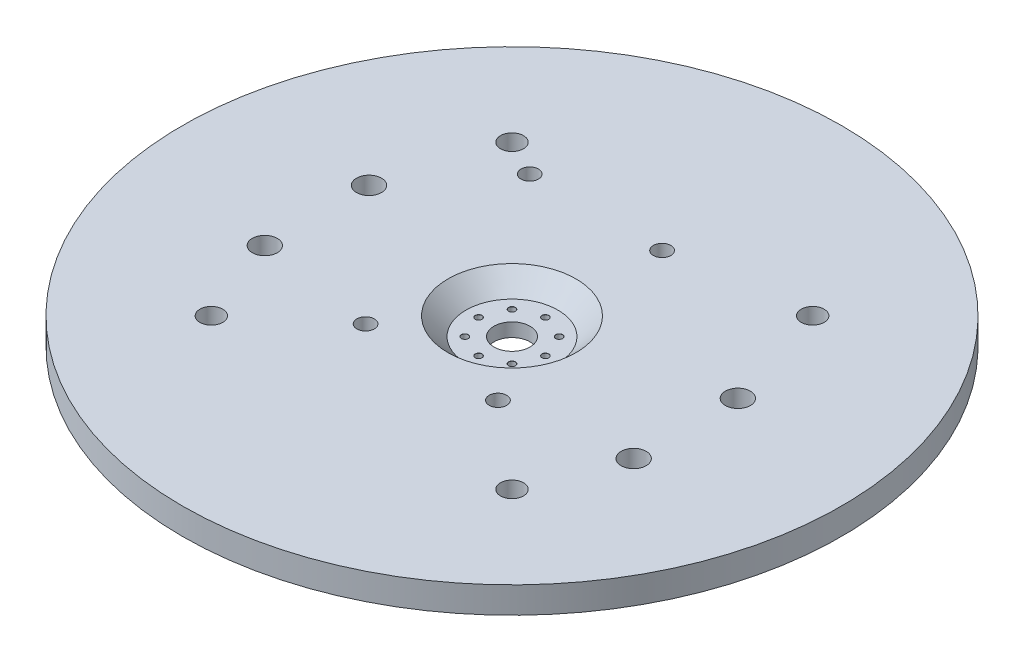
SolidWorks part; units mm, degrees
other "Markup1"
sketch "Sketch21" plane through (-65.5, -15.05, -60) normal (-0.0927, -0.2854, -0.9539) x (0.9951, -0.0609, -0.0785)
material "6061 Alloy"
ref_plane "Front Plane" through (0, 0, 0) normal (0, 0, 1) x (1, 0, 0)
ref_plane "Top Plane" through (0, 0, 0) normal (0, 1, 0) x (1, 0, 0)
ref_plane "Right Plane" through (0, 0, 0) normal (1, 0, 0) x (0, 0, -1)
sketch "Sketch1" plane through (0, 0, 0) normal (0, 1, 0) x (1, 0, 0)
  circle A0 centre (0, 0) radius 79.0575
  dimension "D1" = 158.115
extrude "Boss-Extrude1" add sketch "Sketch1" along normal mid plane 6.3246
sketch "Sketch2" plane through (0, -3.1623, 0) normal (0, -1, 0) x (1, 0, 0)
  circle A0 centre (0, 0) radius 12.065
  circle A1 centre (0, 0) radius 79.0575 construction
  dimension "D1" = 24.13
sketch "Sketch5" plane through (0, 3.1623, 0) normal (0, 1, 0) x (1, 0, 0)
  circle A0 centre (0, 0) radius 10.4
  circle A1 centre (0, 0) radius 79.0575 construction
  dimension "D1" = 20.8
hole_wizard "Tap Drill for M5x0.8 Tap1" positions "Sketch22" profile "Sketch23" hole size "M5x0.8" standard "ANSI Metric" end condition through all
sketch "Sketch22" plane through (0, 3.1623, 0) normal (0, 1, 0) x (1, 0, 0)
  point P0 (-27.3188, 31.5712)
  point P3 (4.4312, 31.5712)
  point P6 (-15.875, -19.2459)
  point P9 (15.875, -19.2459)
  dimension "D1" = 31.75
  dimension "D2" = 31.5712
  dimension "D3" = 4.4312
  dimension "D4" = 31.75
  dimension "D5" = 19.2459
  dimension "D6" = 15.875
sketch "Sketch23" plane through (-27.3188, 3.1623, -31.5712) normal (1, 0, 0) x (0, 0, 1)
  line L0 (0, 0) -> (0, 6.3246)
  line L1 (0, 6.3246) -> (2.1, 6.3246)
  line L2 (2.1, 6.3246) -> (2.1, 0)
  line L5 (2.1, 0) -> (0, 0)
  line L11 (0, -6.35) -> (0, 107.95) construction
  dimension "Thru Hole Dia." = 4.2
  dimension "Thru Hole Depth" = 6.3246
hole_wizard "Tap Drill for M7x1.0 Tap1" positions "Sketch24" profile "Sketch25" hole size "M7x1.0" standard "ANSI Metric" end condition through all
sketch "Sketch24" plane through (0, 3.1623, 0) normal (0, 1, 0) x (1, 0, 0)
  point P0 (-44.245, 9.9416)
  point P3 (-44.245, -15.0584)
  point P6 (44.245, 9.9416)
  point P9 (44.245, -15.0584)
  dimension "D1" = 25
  dimension "D2" = 44.245
  dimension "D3" = 9.9416
  dimension "D4" = 25
  dimension "D5" = 44.245
  dimension "D6" = 15.0584
sketch "Sketch25" plane through (-44.245, 3.1623, -9.9416) normal (1, 0, 0) x (0, 0, 1)
  line L0 (0, 0) -> (0, 6.3246)
  line L1 (0, 6.3246) -> (3, 6.3246)
  line L2 (3, 6.3246) -> (3, 0)
  line L5 (3, 0) -> (0, 0)
  line L11 (0, -6.35) -> (0, 107.95) construction
  dimension "Thru Hole Dia." = 6
  dimension "Thru Hole Depth" = 6.3246
sketch "Sketch28" plane through (0, 3.1623, 0) normal (0, 1, 0) x (1, 0, 0)
  circle A0 centre (0, 0) radius 51
  circle A1 centre (35.8572, -36.2665) radius 4.2952
  dimension "D1" = 102
hole_wizard "M5 Clearance Hole1" positions "Sketch29" profile "Sketch30" hole size "M5" standard "ANSI Metric" end condition through all
sketch "Sketch29" plane through (0, 3.1623, 0) normal (0, 1, 0) x (1, 0, 0)
  line L0 (-36.0624, 36.0624) -> (-36.0624, -36.0624) construction
  line L2 (-36.0624, 36.0624) -> (36.0624, 36.0624) construction
  line L3 (36.0624, 36.0624) -> (36.0624, -36.0624) construction
  line L4 (36.0624, -36.0624) -> (-36.0624, -36.0624) construction
  circle A0 centre (0, 0) radius 51 construction
  point P0 (-36.0624, 36.0624)
  point P4 (-36.0624, -36.0624)
  point P6 (36.0624, -36.0624)
  point P8 (36.0624, 36.0624)
sketch "Sketch30" plane through (-36.0624, 3.1623, -36.0624) normal (1, 0, 0) x (0, 0, 1)
  line L0 (0, 0) -> (0, 6.3246)
  line L1 (0, 6.3246) -> (2.75, 6.3246)
  line L2 (2.75, 6.3246) -> (2.75, 0)
  line L5 (2.75, 0) -> (0, 0)
  line L11 (0, -6.35) -> (0, 107.95) construction
  dimension "Thru Hole Dia." = 5.5
  dimension "Thru Hole Depth" = 6.3246
sketch "Sketch31" plane through (0, 3.1623, 0) normal (0, 1, 0) x (1, 0, 0)
  line L1 (5.6569, 5.6569) -> (-5.6569, 5.6569) construction
  line L2 (5.6569, 5.6569) -> (5.6569, -5.6569) construction
  line L3 (5.6569, -5.6569) -> (-5.6569, -5.6569) construction
  line L4 (-5.6569, 5.6569) -> (-5.6569, -5.6569) construction
  line L5 (5.6569, 5.6569) -> (-5.6569, -5.6569) construction
  line L6 (5.6569, -5.6569) -> (-5.6569, 5.6569) construction
  line L7 (8, 0) -> (0, 8) construction
  line L8 (8, 0) -> (0, -8) construction
  line L9 (0, -8) -> (-8, 0) construction
  line L10 (0, 8) -> (-8, 0) construction
  line L11 (8, 0) -> (-8, 0) construction
  line L12 (0, -8) -> (0, 8) construction
  circle A0 centre (0, 0) radius 8 construction
  point P0 (0, 0)
  point P8 (0, 0)
  dimension "D1" = 16
sketch "Sketch32" plane through (0, 3.1623, 0) normal (0, 1, 0) x (1, 0, 0)
  circle A0 centre (0, 0) radius 11
  circle A1 centre (0, 0) radius 4.3302
  dimension "D1" = 22
  dimension "D2" = 8.6604
extrude "Cut-Extrude1" cut sketch "Sketch32" against normal through all contours A1
extrude "Cut-Extrude2" cut sketch "Sketch32<4>" against normal offset from surface (4.3246 mm away) 2 up to face at (0, -3.1623, 4.3302)
sketch "Sketch32<4>" plane through (0, 3.1623, 0) normal (0, 1, 0) x (1, 0, 0) same geometry as "Sketch32"
chamfer "Chamfer1" distance 4.35 angle 45 1 edges at (0, 3.1623, 11)
hole_wizard "Tap Drill for M2x0.4 Tap1" positions "Sketch33" profile "Sketch34" hole size "M2x0.4" standard "ANSI Metric" end condition through all
sketch "Sketch33" plane through (0, -1.1623, 0) normal (0, 1, 0) x (1, 0, 0)
  point P0 (-8, 0)
  point P3 (-5.6569, 5.6569)
  point P6 (0, 8)
  point P9 (5.6569, 5.6569)
  point P12 (8, 0)
  point P15 (5.6569, -5.6569)
  point P18 (0, -8)
  point P21 (-5.6569, -5.6569)
sketch "Sketch34" plane through (-8, -1.1623, 0) normal (1, 0, 0) x (0, 0, 1)
  line L0 (0, 0) -> (0, 2)
  line L1 (0, 2) -> (0.8, 2)
  line L2 (0.8, 2) -> (0.8, 0.025)
  line L3 (0.8, 0.025) -> (0.825, 0)
  line L5 (0.825, 0) -> (0, 0)
  line L6 (-0.8, 0.025) -> (-0.825, 0) construction
  line L11 (0, -6.35) -> (0, 107.95) construction
  dimension "Thru Hole Dia." = 1.6
  dimension "Thru Hole Depth" = 2
  dimension "Near C'Sink Dia." = 1.65
  dimension "Near C'Sink Angle" = 90
sketch "Sketch35" plane through (0, -3.1623, 0) normal (0, -1, 0) x (1, 0, 0)
  circle A0 centre (0, 0) radius 11
  circle A1 centre (-5.6569, 5.6569) radius 0.8 construction
  circle A2 centre (-8, 0) radius 0.8 construction
  circle A4 centre (-5.6569, -5.6569) radius 0.8 construction
  circle A5 centre (0, -8) radius 0.8 construction
  circle A6 centre (5.6569, -5.6569) radius 0.8 construction
  circle A7 centre (8, 0) radius 0.8 construction
  circle A8 centre (5.6569, 5.6569) radius 0.8 construction
  circle A9 centre (0, 8) radius 0.8 construction
  circle A10 centre (-5.6569, 5.6569) radius 0.8
  circle A11 centre (-8, 0) radius 0.8
  circle A12 centre (-5.6569, -5.6569) radius 0.8
  circle A13 centre (0, -8) radius 0.8
  circle A14 centre (5.6569, -5.6569) radius 0.8
  circle A15 centre (8, 0) radius 0.8
  circle A16 centre (5.6569, 5.6569) radius 0.8
  circle A17 centre (0, 8) radius 0.8
  circle A18 centre (0, 0) radius 4.3302 construction
  circle A19 centre (0, 0) radius 4.3302
  dimension "D1" = 22
extrude "Boss-Extrude3" add sketch "Sketch35" along normal blind 1.27
